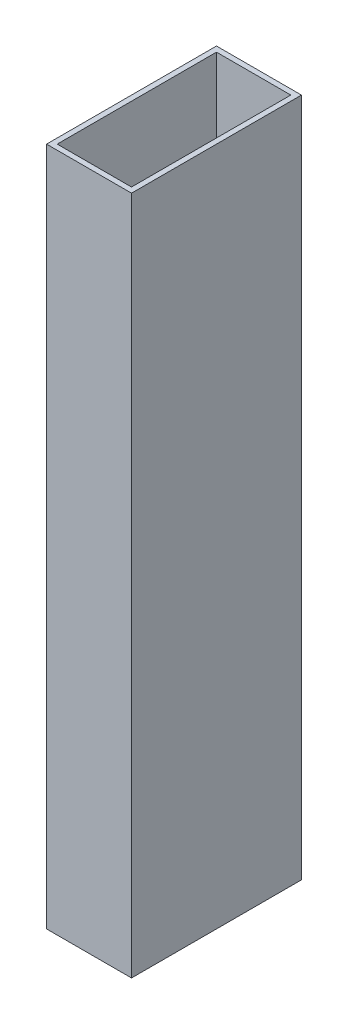
SolidWorks part; units mm, degrees
material "6061-T6 (SS)"
ref_plane "Front" through (0, 0, 0) normal (0, 0, 1) x (1, 0, 0)
ref_plane "Top" through (0, 0, 0) normal (0, 1, 0) x (1, 0, 0)
ref_plane "Right" through (0, 0, 0) normal (1, 0, 0) x (0, 0, -1)
sketch "Sketch1" plane through (0, 0, 0) normal (0, 1, 0) x (1, 0, 0)
  line L1 (12.7, 25.4) -> (-12.7, 25.4)
  line L2 (12.7, 25.4) -> (12.7, -25.4)
  line L3 (12.7, -25.4) -> (-12.7, -25.4)
  line L4 (-12.7, 25.4) -> (-12.7, -25.4)
  line L5 (12.7, 25.4) -> (-12.7, -25.4) construction
  line L6 (12.7, -25.4) -> (-12.7, 25.4) construction
  point P0 (0, 0)
  dimension "D1" = 25.4
  dimension "D2" = 50.8
extrude "Extrude-Thin1" add sketch "Sketch1" along normal up to surface (203.2 mm away) thin thin type one direction reverse wall 1.5875
